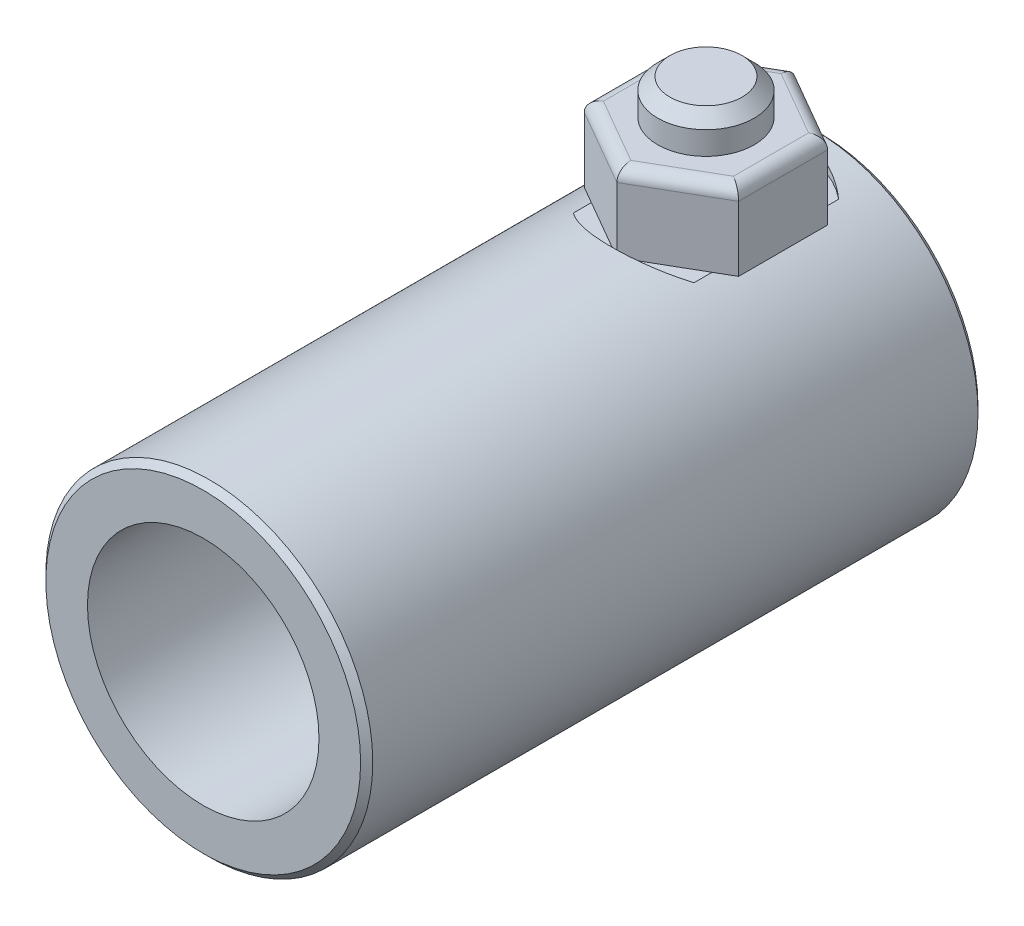
SolidWorks part; units mm, degrees
material "ASTM A36 Steel"
ref_plane "Front Plane" through (0, 0, 0) normal (0, 0, 1) x (1, 0, 0)
ref_plane "Top Plane" through (0, 0, 0) normal (0, 1, 0) x (1, 0, 0)
ref_plane "Right Plane" through (0, 0, 0) normal (1, 0, 0) x (0, 0, -1)
sketch "Sketch1" plane through (0, 0, 0) normal (0, 0, 1) x (1, 0, 0)
  circle A0 centre (0, 0) radius 13.45
  dimension "D1" = 26.9
extrude "Boss-Extrude1" add sketch "Sketch1" along normal blind 25.4 and the other way blind 25.4
sketch "Sketch2" plane through (0, 0, 25.4) normal (0, 0, 1) x (1, 0, 0)
  circle A0 centre (0, 0) radius 9.525
  dimension "D1" = 19.05
extrude "Cut-Extrude1" cut sketch "Sketch2" against normal blind 25.4
sketch "Sketch3" plane through (0, 0, -25.4) normal (0, 0, -1) x (-1, 0, 0)
  circle A0 centre (0, 0) radius 7.9375
  dimension "D1" = 15.875
extrude "Cut-Extrude2" cut sketch "Sketch3" against normal through all
sketch "Sketch4" plane through (0, 0, 0) normal (0, 1, 0) x (1, 0, 0)
  line L0 (0, 0) -> (0, 15.9687) construction
  line L1 (0, 12) -> (16.8423, 12) construction
  line L3 (13.45, 25.4) -> (-13.45, 25.4) construction
  circle A0 centre (0, 15.9687) radius 3.9688
  dimension "D1" = 7.9375
  dimension "D2" = 13.4
extrude "Boss-Extrude2" add sketch "Sketch4" along normal blind 15.6 from offset 6.15
sketch "Sketch5" plane through (0, 0, 0) normal (0, 1, 0) x (1, 0, 0)
  circle A0 centre (0, 15.9687) radius 3.9688
  circle A1 centre (0, 15.9687) radius 7.75
  circle A2 centre (0, 15.9687) radius 3.9688 construction
  dimension "D1" = 15.5
extrude "Cut-Extrude4" cut sketch "Sketch5" along normal through all from offset 12.5
sketch "Sketch6" plane through (0, 12.5, 0) normal (0, 1, 0) x (1, 0, 0)
  line L0 (0, 0) -> (0, 15.9687) construction
  line L2 (6.35, 12.3026) -> (6.35, 19.6349)
  line L3 (6.35, 19.6349) -> (0, 23.3011)
  line L4 (0, 23.3011) -> (-6.35, 19.6349)
  line L5 (-6.35, 19.6349) -> (-6.35, 12.3026)
  line L6 (-6.35, 12.3026) -> (0, 8.6364)
  line L7 (0, 8.6364) -> (6.35, 12.3026)
  circle A0 centre (0, 15.9687) radius 3.9688 construction
  circle A1 centre (0, 15.9687) radius 6.35 construction
  dimension "D1" = 12.7
extrude "Boss-Extrude3" add sketch "Sketch6" along normal blind 6.35 separate body
fillet "Fillet1" radius 1 6 edges at (-3.175, 18.85, -10.4695) (-6.35, 18.85, -15.9687) (-3.175, 18.85, -21.468) (3.175, 18.85, -21.468) (6.35, 18.85, -15.9687) (3.175, 18.85, -10.4695)
chamfer "Chamfer1" distance 1 angle 45 1 edges at (0, 21.75, -12)
chamfer "Chamfer2" distance 0.5 angle 45 2 edges at (13.45, 0, -25.4) (13.45, 0, 25.4)
